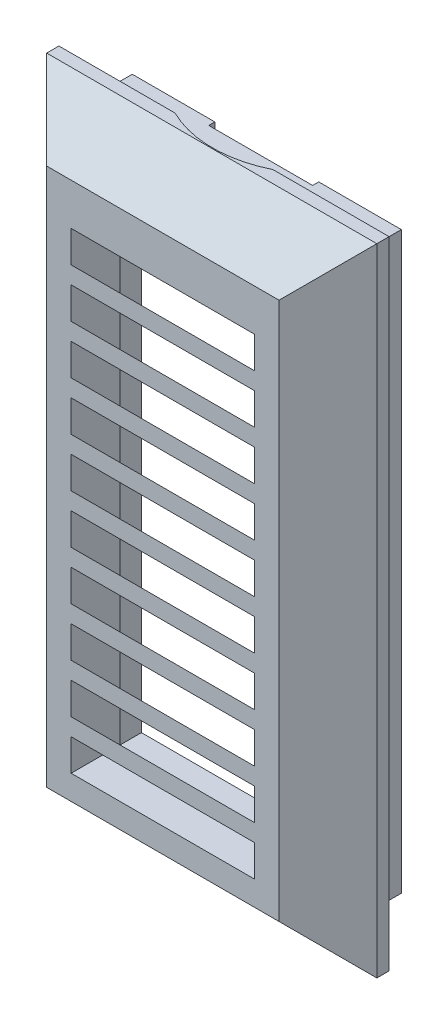
SolidWorks part; units mm, degrees
ref_plane "Front Plane" through (0, 0, 0) normal (0, 0, 1) x (1, 0, 0)
ref_plane "Top Plane" through (0, 0, 0) normal (0, 1, 0) x (1, 0, 0)
ref_plane "Right Plane" through (0, 0, 0) normal (1, 0, 0) x (0, 0, -1)
sketch "Sketch1" plane through (0, 0, 0) normal (0, 0, 1) x (1, 0, 0)
  line L1 (-21.5164, 36.087) -> (32.4836, 36.087)
  line L2 (-21.5164, 36.087) -> (-21.5164, -67.913)
  line L3 (-21.5164, -67.913) -> (32.4836, -67.913)
  line L4 (32.4836, 36.087) -> (32.4836, -67.913)
  line L5 (-9.5164, 24.087) -> (20.4836, 24.087)
  line L6 (-9.5164, 24.087) -> (-9.5164, -55.913)
  line L7 (-9.5164, -55.913) -> (20.4836, -55.913)
  line L8 (20.4836, 24.087) -> (20.4836, -55.913)
  dimension "D1" = 54
  dimension "D2" = 104
  dimension "D3" = 12
  dimension "D4" = 12
  dimension "D5" = 12
  dimension "D6" = 12
extrude "Boss-Extrude1" add sketch "Sketch1" along normal blind 8
chamfer "Chamfer1" distance 8 angle 45 4 edges at (-21.5164, -15.913, 8) (5.4836, 36.087, 8) (32.4836, -15.913, 8) (5.4836, -67.913, 8)
sketch "Sketch2" plane through (0, 0, 0) normal (0, 0, -1) x (-1, 0, 0)
  line L1 (21.5164, -67.913) -> (-32.4836, -67.913)
  line L2 (21.5164, -67.913) -> (21.5164, 36.087)
  line L3 (21.5164, 36.087) -> (-32.4836, 36.087)
  line L4 (-32.4836, -67.913) -> (-32.4836, 36.087)
  line L5 (19.5164, -65.913) -> (-30.4836, -65.913)
  line L6 (19.5164, -65.913) -> (19.5164, 34.087)
  line L7 (19.5164, 34.087) -> (-30.4836, 34.087)
  line L8 (-30.4836, -65.913) -> (-30.4836, 34.087)
  dimension "D1" = 2
  dimension "D2" = 2
  dimension "D3" = 2
  dimension "D4" = 2
extrude "Boss-Extrude2" add sketch "Sketch2" along normal blind 2
sketch "Sketch3" plane through (0, 0, 0) normal (0, 0, -1) x (-1, 0, 0)
  line L0 (-30.4836, -65.913) -> (19.5164, -65.913) construction
  line L1 (16.5164, -62.913) -> (-27.4836, -62.913)
  line L2 (16.5164, -62.913) -> (16.5164, 31.087)
  line L3 (16.5164, 31.087) -> (-27.4836, 31.087)
  line L4 (-27.4836, -62.913) -> (-27.4836, 31.087)
  line L5 (-30.4836, 34.087) -> (-30.4836, -65.913) construction
  line L6 (19.5164, -65.913) -> (19.5164, 34.087) construction
  line L7 (19.5164, 34.087) -> (-30.4836, 34.087) construction
  line L9 (15.0164, -61.413) -> (-25.9836, -61.413)
  line L10 (15.0164, -61.413) -> (15.0164, 29.587)
  line L11 (15.0164, 29.587) -> (-25.9836, 29.587)
  line L12 (-25.9836, -61.413) -> (-25.9836, 29.587)
  dimension "D1" = 3
  dimension "D2" = 3
  dimension "D3" = 3
  dimension "D4" = 3
  dimension "D5" = 1.5
  dimension "D6" = 1.5
  dimension "D7" = 1.5
  dimension "D8" = 1.5
extrude "Boss-Extrude3" add sketch "Sketch3" along normal blind 9
sketch "Sketch4" plane through (0, 31.087, 0) normal (0, 1, 0) x (1, 0, 0)
  line L0 (-16.5164, 9) -> (27.4836, 9) construction
  line L1 (-3.0164, 9) -> (13.9836, 9)
  line L2 (-3.0164, 9) -> (-3.0164, 8)
  line L3 (-3.0164, 8) -> (13.9836, 8)
  line L4 (13.9836, 9) -> (13.9836, 8)
  line L5 (-16.5164, 9) -> (-16.5164, 0) construction
  dimension "D1" = 13.5
  dimension "D2" = 17
  dimension "D3" = 1
extrude "Cut-Extrude1" cut sketch "Sketch4" against normal up to next
sketch "Sketch5" plane through (0, 36.087, 0) normal (0, 1, 0) x (1, 0, 0)
  line L0 (-21.5164, 2) -> (32.4836, 2) construction
  line L1 (-21.5164, 2) -> (-21.5164, 0) construction
  arc A0 (-2.5164, 2) -> (13.4836, 2) centre (5.4836, 18.1245) ccw
  dimension "D1" = 19
  dimension "D2" = 16
extrude "Cut-Extrude2" cut sketch "Sketch5" against normal blind 2 and the other way through all
sketch "Sketch6" plane through (20.4836, 0, 0) normal (-1, 0, 0) x (0, 0, 1)
  line L0 (0, -55.913) -> (8, -47.913)
  line L1 (8, -55.913) -> (8, 24.087) construction
  line L2 (0, -55.913) -> (0, 24.087) construction
  line L3 (2.8284, -55.913) -> (8, -50.7414)
  line L4 (8, -55.913) -> (0, -55.913) construction
  line L5 (8, -50.7414) -> (8, -47.913)
  line L6 (0, -50.7414) -> (8, -42.7414)
  line L7 (0, -47.913) -> (8, -39.913)
  line L8 (8, -39.913) -> (8, -42.7414)
  line L9 (2.8284, -55.913) -> (0, -55.913)
  line L10 (0, -50.7414) -> (0, -47.913)
  line L11 (0, -42.7414) -> (0, -39.913)
  line L12 (0, -39.913) -> (8, -31.913)
  line L13 (8, -31.913) -> (8, -34.7414)
  line L14 (0, -42.7414) -> (8, -34.7414)
  line L15 (0, -34.7414) -> (0, -31.913)
  line L16 (0, -31.913) -> (8, -23.913)
  line L17 (8, -23.913) -> (8, -26.7414)
  line L18 (0, -34.7414) -> (8, -26.7414)
  line L19 (0, -26.7414) -> (0, -23.913)
  line L20 (0, -23.913) -> (8, -15.913)
  line L21 (8, -15.913) -> (8, -18.7414)
  line L22 (0, -26.7414) -> (8, -18.7414)
  line L23 (0, -18.7414) -> (0, -15.913)
  line L24 (0, -15.913) -> (8, -7.913)
  line L25 (8, -7.913) -> (8, -10.7414)
  line L26 (0, -18.7414) -> (8, -10.7414)
  line L27 (0, -10.7414) -> (0, -7.913)
  line L28 (0, -7.913) -> (8, 0.087)
  line L29 (8, 0.087) -> (8, -2.7414)
  line L30 (0, -10.7414) -> (8, -2.7414)
  line L31 (0, -2.7414) -> (0, 0.087)
  line L32 (0, 0.087) -> (8, 8.087)
  line L33 (8, 8.087) -> (8, 5.2586)
  line L34 (0, -2.7414) -> (8, 5.2586)
  line L35 (0, 5.2586) -> (0, 8.087)
  line L36 (0, 8.087) -> (8, 16.087)
  line L37 (8, 16.087) -> (8, 13.2586)
  line L38 (0, 5.2586) -> (8, 13.2586)
  line L41 (8, 24.087) -> (8, 21.2586)
  line L42 (0, 13.2586) -> (8, 21.2586)
  line L43 (0, 16.087) -> (8, 24.087) [skipped]
  line L44 (0, 13.2586) -> (0, 16.087) [skipped]
  line L45 (0, 13.2586) -> (0, 20.3027)
  line L46 (0, 20.3027) -> (3.7844, 24.087)
  line L47 (8, 24.087) -> (0, 24.087) construction
  line L48 (3.7844, 24.087) -> (8, 24.087)
  dimension "D1" = 45
  dimension "D2" = 2
  dimension "D3" = 2
  dimension "D4" = 9
extrude "Boss-Extrude4" add sketch "Sketch6" along normal up to next
